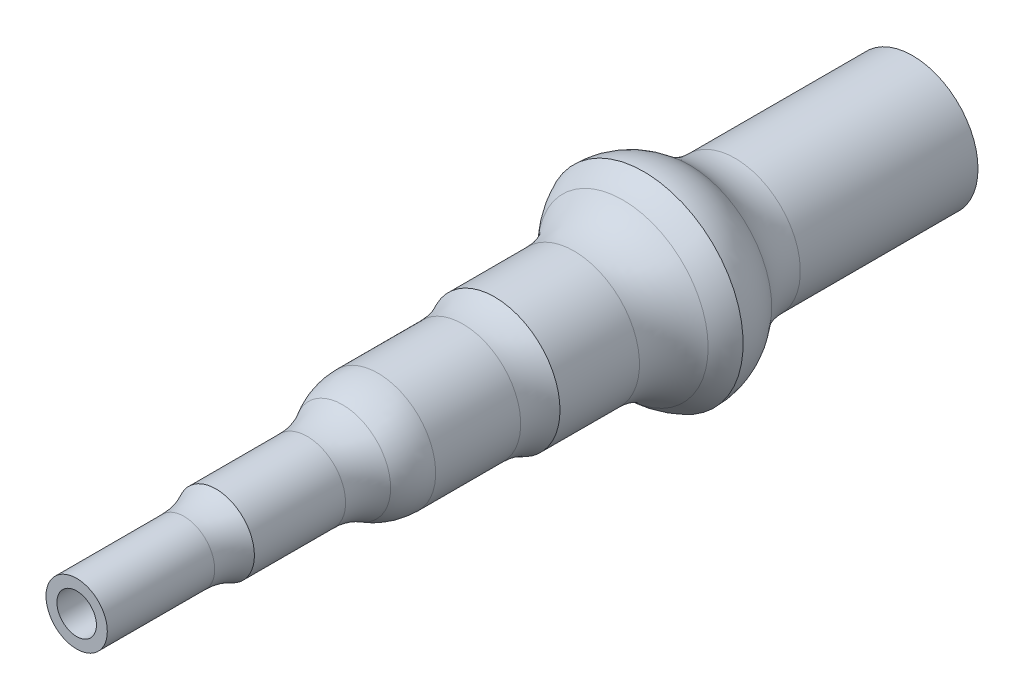
SolidWorks part; units mm, degrees
ref_plane "Front Plane" through (0, 0, 0) normal (0, 0, 1) x (1, 0, 0)
ref_plane "Top Plane" through (0, 0, 0) normal (0, 1, 0) x (1, 0, 0)
ref_plane "Right Plane" through (0, 0, 0) normal (1, 0, 0) x (0, 0, -1)
sketch "Sketch1" plane through (0, 0, 0) normal (0, 0, 1) x (1, 0, 0)
  circle A2 centre (0, 0) radius 2.2
  circle A3 centre (0, 0) radius 4.69
  dimension "D1" = 4.4
extrude "Boss-Extrude3" add sketch "Sketch1" along normal blind 30
sketch "Sketch3" plane through (0, 0, 30) normal (0, 0, 1) x (1, 0, 0)
  circle A0 centre (0, 0) radius 4.1433
  circle A1 centre (0, 0) radius 2.7398
extrude "Boss-Extrude4" add sketch "Sketch3" along normal blind 10
sketch "Sketch4" plane through (0, 0, 40) normal (0, 0, 1) x (1, 0, 0)
  circle A0 centre (0, 0) radius 2.7572
  circle A2 centre (0, 0) radius 1.674
extrude "Boss-Extrude5" add sketch "Sketch4" along normal blind 10
sketch "Sketch5" plane through (0, 0, 50) normal (0, 0, 1) x (1, 0, 0)
  circle A0 centre (0, 0) radius 2.2
  circle A1 centre (0, 0) radius 1.4177
  dimension "D1" = 4.4
extrude "Boss-Extrude6" add sketch "Sketch5" along normal blind 10
fillet "Fillet13" radius 5 1 edges at (1.4177, 0, 50)
fillet "Fillet15" radius 5 1 edges at (1.674, 0, 50)
fillet "Fillet16" radius 5 1 edges at (2.2, 0, 50)
fillet "Fillet17" radius 5 1 edges at (1.674, 0, 40)
fillet "Fillet18" radius 5 1 edges at (2.7572, 0, 40)
fillet "Fillet19" radius 5 1 edges at (2.7398, 0, 40)
fillet "Fillet20" radius 5 1 edges at (4.1433, 0, 40)
fillet "Fillet21" radius 5 1 edges at (4.1433, 0, 30)
sketch "Sketch6" plane through (0, 0, 0) normal (0, 0, -1) x (-1, 0, 0)
  circle A1 centre (0, 0) radius 7.1301
extrude "Boss-Extrude7" add sketch "Sketch6" along normal blind 5 from offset 20 offset against normal yes
sketch "Sketch7" plane through (0, 0, 0) normal (0, 0, -1) x (-1, 0, 0)
  circle A0 centre (0, 0) radius 3.7687
extrude "Cut-Extrude1" cut sketch "Sketch7" against normal blind 30
fillet "Fillet26" radius 5 1 edges at (-4.69, 0, 20)
fillet "Fillet27" radius 5 1 edges at (-7.1301, 0, 15)
fillet "Fillet28" radius 5 2 edges at (-7.1301, 0, 20) (-4.69, 0, 15)
fillet "Fillet29" radius 5 1 edges at (-2.7398, 0, 30)
fillet "Fillet30" radius 5 1 edges at (-3.7687, 0, 30)
